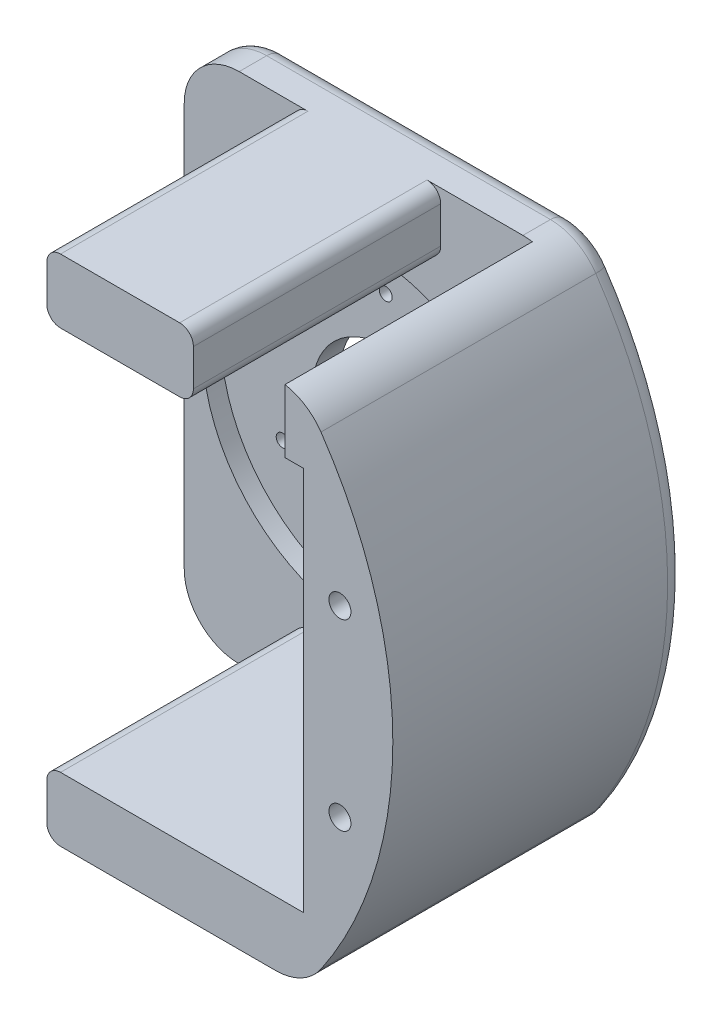
SolidWorks part; units mm, degrees
ref_plane "Спереди" through (0, 0, 0) normal (0, 0, 1) x (1, 0, 0)
ref_plane "Сверху" through (0, 0, 0) normal (0, 1, 0) x (1, 0, 0)
ref_plane "Справа" through (0, 0, 0) normal (1, 0, 0) x (0, 0, -1)
other "Configuration Table"
sketch "Эскиз1" plane through (0, 0, 0) normal (0, 0, 1) x (1, 0, 0)
  line L2 (0, 28) -> (49.7722, 28) construction
  line L3 (0, 0) -> (40, 0)
  line L4 (0, 0) -> (0, 56)
  line L5 (0, 56) -> (40, 56)
  arc A5 (40, 0) -> (40, 56) centre (4.7722, 28) ccw
  circle A6 centre (20, 28) radius 8
  circle A7 centre (20, 28) radius 18
  dimension "D2" = 56
  dimension "D4" = 20
  dimension "D10" = 45
  dimension "D3" = 16
  dimension "D5" = 36
  dimension "D13" = 40
extrude "Бобышка-Вытянуть1" add sketch "Эскиз1" against normal blind 3 contours L2 L4 L3 A5 A7 | L4 L2 A7 A5 L5 | A7 L2 A6 | L2 A7 A6 region at (20, 36.6841, 0) region at (20, 19.3159, 0) region at (25.6064, 45.2779, 0) region at (25.6064, 10.7221, 0)
hole_wizard "Отверстие с зазором M1.21" positions "Эскиз3" profile "Эскиз4" hole size "M1.2" standard "ISO"
sketch "Эскиз3" plane through (0, 0, 0) normal (0, 0, 1) x (1, 0, 0)
  circle A0 centre (20, 28) radius 8 construction
  circle A1 centre (20, 28) radius 8
  point P0 (20, 41)
  point P12 (31.2583, 34.5)
  point P13 (31.2583, 21.5)
  point P14 (20, 15)
  point P15 (8.7417, 21.5)
  point P16 (8.7417, 34.5)
  dimension "D1" = 13
  dimension "D2" = 6
sketch "Эскиз4" plane through (20, 41, 0) normal (1, 0, 0) x (0, -1, 0)
  line L0 (0, 0) -> (0, 10)
  line L1 (0, 10) -> (0.7, 9.5794)
  line L2 (0.7, 9.5794) -> (0.7, 0)
  line L5 (0.7, 0) -> (0, 0)
  line L10 (0, 10) -> (-0.7, 9.5794) construction
  line L11 (0, -6.35) -> (0, 107.95) construction
  dimension "Диаметр отверстия" = 1.4
  dimension "Глубина отверстия" = 10
  dimension "Угол заточки сверла" = 118
extrude "Бобышка-Вытянуть2" add sketch "Эскиз1<3>" along normal blind 2 contours L2 L4 L3 A5 A7 | L4 L2 A7 A5 L5 region at (25.6064, 45.2779, 0) region at (25.6064, 10.7221, 0)
sketch "Эскиз1<3>" plane through (0, 0, 0) normal (0, 0, 1) x (1, 0, 0) same geometry as "Эскиз1"
sketch "Эскиз2" plane through (0, 0, 2) normal (0, 0, 1) x (1, 0, 0)
  line L0 (40, 0) -> (12, 0)
  line L1 (0, 0) -> (40, 0) construction
  line L2 (12, 0) -> (12, 7)
  line L3 (12, 7) -> (40, 7)
  line L6 (38, 49) -> (38, 56)
  line L7 (0, 56) -> (40, 56) construction
  line L8 (38, 56) -> (40, 56)
  line L10 (12, 56) -> (28, 56)
  line L11 (12, 56) -> (12, 49)
  line L12 (12, 49) -> (28, 49)
  line L13 (28, 56) -> (28, 49)
  line L14 (40, 7) -> (40, 49)
  line L15 (40, 49) -> (38, 49)
  arc A0 (40, 0) -> (40, 56) centre (4.7722, 28) ccw construction
  arc A1 (40, 0) -> (40, 56) centre (4.7722, 28) ccw
  point P9 (42.0983, 49)
  point P18 (38, 52.5)
  dimension "D1" = 7
  dimension "D2" = 7
  dimension "D3" = 28
  dimension "D4" = 28
  dimension "D5" = 10
  dimension "D6" = 16
extrude "Бобышка-Вытянуть3" add sketch "Эскиз2" along normal blind 27
fillet "Скругление1" radius 6 4 edges at (40, 56, 13) (40, 0, 13) (0, 0, -0.5) (0, 56, -0.5)
fillet "Скругление3" radius 1.5 6 edges at (12, 0, 15.5) (12, 7, 15.5) (28, 56, 15.5) (28, 49, 15.5) (12, 56, 15.5) (12, 49, 15.5)
hole_wizard "Отверстие с зазором M21" positions "Эскиз5" profile "Эскиз6" hole size "M2" standard "ISO"
sketch "Эскиз5" plane through (0, 0, 29) normal (0, 0, 1) x (1, 0, 0)
  line L0 (40, 28) -> (49.7722, 28) construction
  line L1 (40, 49) -> (40, 7) construction
  arc A0 (41.9289, 2.6154) -> (41.9289, 53.3846) centre (4.7722, 28) ccw construction
  point P24 (44, 38)
  point P26 (44, 18)
  point P39 (0, 0)
  dimension "D1" = 20
  dimension "D2" = 4
sketch "Эскиз6" plane through (44, 38, 29) normal (1, 0, 0) x (0, -1, 0)
  line L0 (0, 0) -> (0, 10)
  line L1 (0, 10) -> (1.2, 9.279)
  line L2 (1.2, 9.279) -> (1.2, 0)
  line L5 (1.2, 0) -> (0, 0)
  line L10 (0, 10) -> (-1.2, 9.279) construction
  line L11 (0, -6.35) -> (0, 107.95) construction
  dimension "Диаметр отверстия" = 2.4
  dimension "Глубина отверстия" = 10
  dimension "Угол заточки сверла" = 118
hole_wizard "Отверстие с зазором M1.22" positions "Эскиз7" profile "Эскиз8" hole size "M1.2" standard "ISO"
sketch "Эскиз7" plane through (12, 0, 0) normal (-1, 0, 0) x (0, 0, 1)
  arc A0 (9.9307, 54.5) -> (12.0693, 54.5) centre (11, 52.2402) ccw construction
  arc A2 (18.9307, 54.5) -> (21.0693, 54.5) centre (20, 52.2402) ccw construction
  arc A3 (12.0693, 1.5) -> (9.9307, 1.5) centre (11, 3.7598) ccw construction
  arc A4 (21.0693, 1.5) -> (18.9307, 1.5) centre (20, 3.7598) ccw construction
  point P0 (20, 52.2402)
  point P2 (11, 52.2402)
  point P15 (20, 3.7598)
  point P17 (11, 3.7598)
sketch "Эскиз8" plane through (12, 52.2402, 20) normal (0, 1, 0) x (0, 0, 1)
  line L0 (0, 0) -> (0, 10)
  line L1 (0, 10) -> (0.7, 9.5794)
  line L2 (0.7, 9.5794) -> (0.7, 0)
  line L5 (0.7, 0) -> (0, 0)
  line L10 (0, 10) -> (-0.7, 9.5794) construction
  line L11 (0, -6.35) -> (0, 107.95) construction
  dimension "Диаметр отверстия" = 1.4
  dimension "Глубина отверстия" = 10
  dimension "Угол заточки сверла" = 118
fillet "Скругление4" radius 2 8 edges at (39.7758, 0.694, -3) (21.4873, 0, -3) (1.7574, 1.7574, -3) (0, 28, -3) (1.7574, 54.2426, -3) (21.4873, 56, -3) (39.7758, 55.306, -3) (49.7722, 28, -3)
